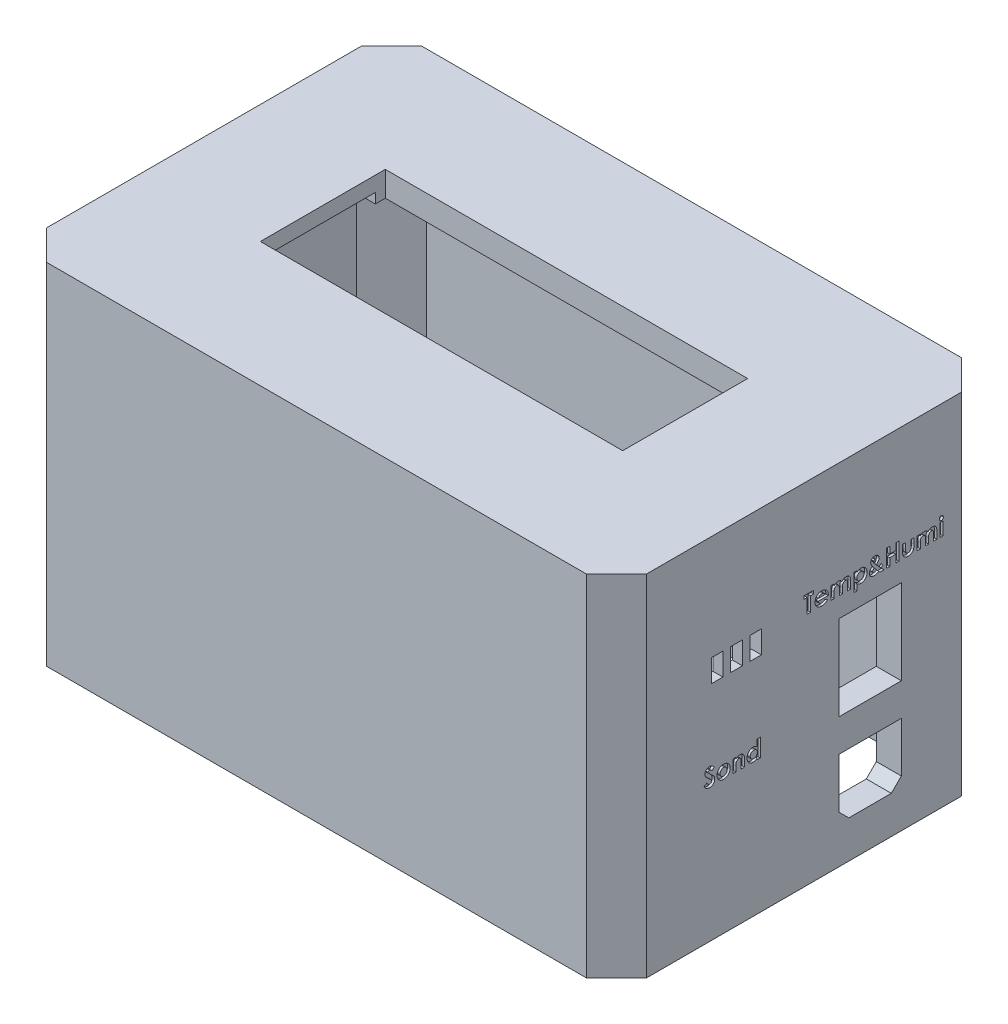
SolidWorks part; units mm, degrees
material "ABS"
ref_plane "Front Plane" through (0, 0, 0) normal (0, 0, 1) x (1, 0, 0)
ref_plane "Top Plane" through (0, 0, 0) normal (0, 1, 0) x (1, 0, 0)
ref_plane "Right Plane" through (0, 0, 0) normal (1, 0, 0) x (0, 0, -1)
sketch "Sketch1" plane through (0, 0, 0) normal (0, 1, 0) x (1, 0, 0)
  line L1 (-55, -32.5) -> (55, -32.5)
  line L2 (-55, -32.5) -> (-55, 32.5)
  line L3 (-55, 32.5) -> (55, 32.5)
  line L4 (55, -32.5) -> (55, 32.5)
  line L5 (-55, -32.5) -> (55, 32.5) construction
  line L6 (-55, 32.5) -> (55, -32.5) construction
  line L7 (-60, -37.5) -> (60, -37.5)
  line L8 (-60, -37.5) -> (-60, 37.5)
  line L9 (-60, 37.5) -> (60, 37.5)
  line L10 (60, -37.5) -> (60, 37.5)
  line L11 (-60, -37.5) -> (60, 37.5) construction
  line L12 (-60, 37.5) -> (60, -37.5) construction
  point P0 (0, 0)
  point P6 (0, 0)
  dimension "D1" = 110
  dimension "D2" = 65
  dimension "D3" = 5
  dimension "D4" = 5
extrude "Boss-Extrude1" add sketch "Sketch1" along normal blind 65
sketch "Sketch2" plane through (0, 65, 0) normal (0, 1, 0) x (1, 0, 0)
  line L1 (-60, 37.5) -> (60, 37.5)
  line L2 (-60, 37.5) -> (-60, -37.5)
  line L3 (-60, -37.5) -> (60, -37.5)
  line L4 (60, 37.5) -> (60, -37.5)
extrude "Boss-Extrude2" add sketch "Sketch2" along normal blind 5
chamfer "Chamfer1" distance 6 angle 45 4 edges at (60, 35, 37.5) (60, 35, -37.5) (-60, 35, -37.5) (-60, 35, 37.5)
chamfer "Chamfer2" distance 7 angle 45 4 edges at (-55, 32.5, -32.5) (55, 32.5, -32.5) (-55, 32.5, 32.5) (55, 32.5, 32.5)
sketch "Sketch3" plane through (0, 0, 0) normal (0, -1, 0) x (1, 0, 0)
  line L0 (-54, 37.5) -> (54, 37.5) construction
  line L1 (60, 31.5) -> (60, -31.5) construction
  line L2 (54, -37.5) -> (-54, -37.5) construction
  line L3 (-60, -31.5) -> (-60, 31.5) construction
  circle A0 centre (54.5, 32) radius 1.4
  circle A1 centre (-54.5, 32) radius 1.4
  circle A2 centre (-54.5, -32) radius 1.4
  circle A3 centre (54.5, -32) radius 1.4
  dimension "D1" = 2.8
  dimension "D2" = 5.5
  dimension "D3" = 5.5
  dimension "D4" = 2.8
  dimension "D6" = 5.5
  dimension "D7" = 2.8
  dimension "D8" = 5.5
  dimension "D9" = 5.5
  dimension "D10" = 2.8
  dimension "D11" = 5.5
  dimension "D12" = 5.5
  dimension "D5" = 5.5
extrude "Cut-Extrude1" cut sketch "Sketch3" against normal blind 35
chamfer "Chamfer3" distance 1.2 angle 45 4 edges at (-54.5, 35, -33.4) (54.5, 35, -33.4) (54.5, 35, 30.6) (-54.5, 35, 30.6)
sketch "Sketch4" plane through (0, 70, 0) normal (0, 1, 0) x (1, 0, 0)
  line L1 (36.25, -12.5) -> (-36.25, -12.5)
  line L2 (36.25, -12.5) -> (36.25, 12.5)
  line L3 (36.25, 12.5) -> (-36.25, 12.5)
  line L4 (-36.25, -12.5) -> (-36.25, 12.5)
  line L5 (36.25, -12.5) -> (-36.25, 12.5) construction
  line L6 (36.25, 12.5) -> (-36.25, -12.5) construction
  point P0 (0, 0)
  dimension "D1" = 72.5
  dimension "D2" = 25
extrude "Cut-Extrude2" cut sketch "Sketch4" against normal blind 5
sketch "Sketch5" plane through (0, 65, 0) normal (0, -1, 0) x (1, 0, 0)
  line L0 (-36.25, -12.5) -> (-36.25, 12.5) construction
  line L1 (-36.25, 10.5) -> (-44.25, 10.5)
  line L2 (-36.25, 10.5) -> (-36.25, -10.5)
  line L3 (-36.25, -10.5) -> (-44.25, -10.5)
  line L4 (-44.25, 10.5) -> (-44.25, -10.5)
  line L5 (-36.25, 12.5) -> (36.25, 12.5) construction
  line L6 (36.25, -12.5) -> (-36.25, -12.5) construction
  dimension "D1" = 2
  dimension "D2" = 2
  dimension "D3" = 8
extrude "Cut-Extrude3" cut sketch "Sketch5" against normal blind 2
chamfer "Chamfer4" distance 5 angle 45 2 edges at (-44.25, 66, -10.5) (-44.25, 66, 10.5)
sketch "Sketch6" plane through (60, 0, 0) normal (1, 0, 0) x (0, 0, -1)
  line L0 (31.5, 0) -> (31.5, 70) construction
  line L1 (7, 43) -> (19.5, 43)
  line L2 (7, 43) -> (7, 26)
  line L3 (7, 26) -> (19.5, 26)
  line L4 (19.5, 43) -> (19.5, 26)
  line L5 (7, 19.5) -> (19.5, 19.5)
  line L6 (7, 19.5) -> (7, 7.5)
  line L7 (7, 7.5) -> (19.5, 7.5)
  line L8 (19.5, 19.5) -> (19.5, 7.5)
  line L10 (-31.5, 70) -> (31.5, 70) construction
  dimension "D1" = 12.5
  dimension "D2" = 17
  dimension "D3" = 6.5
  dimension "D4" = 12.5
  dimension "D5" = 12
  dimension "D6" = 12
  dimension "D7" = 27
extrude "Cut-Extrude4" cut sketch "Sketch6" against normal blind 5
chamfer "Chamfer5" distance 2 angle 45 2 edges at (57.5, 7.5, -7) (57.5, 7.5, -19.5)
sketch "Sketch7" plane through (60, 0, 0) normal (1, 0, 0) x (0, 0, -1)
  text T0 "<b>Temp&Humi</b>"
extrude "Cut-Extrude6" cut sketch "Sketch7" against normal blind 0.5
sketch "Sketch8" plane through (60, 0, 0) normal (1, 0, 0) x (0, 0, -1)
  line L0 (19.5, 43) -> (7, 43) construction
  line L1 (-14.5, 43) -> (-12.5, 43)
  line L2 (-14.5, 43) -> (-14.5, 34)
  line L3 (-14.5, 34) -> (-12.5, 34)
  line L4 (-12.5, 43) -> (-12.5, 34)
  line L5 (-31.5, 70) -> (-31.5, 0) construction
  dimension "D1" = 0
  dimension "D2" = 9
  dimension "D3" = 2
  dimension "D4" = 17
extrude "Cut-Extrude7" cut sketch "Sketch8" against normal blind 5
sketch "Sketch9" plane through (0, 43, 0) normal (0, -1, 0) x (1, 0, 0)
  line L0 (55, 12.5) -> (55, 14.5) construction
  circle A0 centre (55, 13.5) radius 5
  dimension "D1" = 10
extrude "Cut-Extrude8" cut sketch "Sketch9" along normal blind 9
sketch "Sketch10" plane through (60, 0, 0) normal (1, 0, 0) x (0, 0, -1)
  line L0 (-14.5, 43) -> (-14.5, 34) construction
  line L1 (-16, 43) -> (-11, 43)
  line L2 (-16, 43) -> (-16, 34)
  line L3 (-16, 34) -> (-11, 34)
  line L4 (-11, 43) -> (-11, 34)
  line L5 (-12.5, 34) -> (-12.5, 43) construction
  dimension "D1" = 1.5
  dimension "D2" = 1.5
extrude "Cut-Extrude9" cut sketch "Sketch10" against normal blind 9
sketch "Sketch11" plane through (55, 0, 0) normal (-1, 0, 0) x (0, 0, 1)
  line L0 (8.5, 34) -> (8.5, 43) construction
  line L1 (6.5, 43) -> (20.5, 43)
  line L2 (6.5, 43) -> (6.5, 51)
  line L3 (6.5, 51) -> (20.5, 51)
  line L4 (20.5, 43) -> (20.5, 51)
  line L5 (18.5, 43) -> (18.5, 34) construction
  dimension "D1" = 2
  dimension "D2" = 2
  dimension "D3" = 8
extrude "Boss-Extrude4" add sketch "Sketch11" along normal blind 6
sketch "Sketch12" plane through (60, 0, 0) normal (1, 0, 0) x (0, 0, -1)
  line L1 (-18.5, 43) -> (-8.5, 43)
  line L2 (-18.5, 43) -> (-18.5, 49)
  line L3 (-18.5, 49) -> (-8.5, 49)
  line L4 (-8.5, 43) -> (-8.5, 49)
  line L5 (-11, 43) -> (-16, 43) construction
  line L6 (-11, 34) -> (-11, 43) construction
  dimension "D1" = 10
  dimension "D2" = 0
  dimension "D3" = 2.5
  dimension "D4" = 6
extrude "Cut-Extrude10" cut sketch "Sketch12" against normal blind 9
chamfer "Chamfer6" distance 6 angle 45 1 edges at (51, 49, 13.5)
chamfer "Chamfer7" distance 6 angle 45 1 edges at (49, 51, 13.5)
sketch "Sketch14" plane through (60, 0, 0) normal (1, 0, 0) x (0, 0, -1)
  line L0 (-8.5, 43) -> (-8.5, 49) construction
  line L1 (-18.5, 43) -> (-8.5, 43)
  line L2 (-18.5, 43) -> (-18.5, 44.5)
  line L3 (-18.5, 44.5) -> (-16.2, 44.5)
  line L4 (-8.5, 43) -> (-8.5, 44.5)
  line L5 (-8.5, 49) -> (-18.5, 49) construction
  line L6 (-16.2, 49) -> (-14.7, 49)
  line L7 (-16.2, 49) -> (-16.2, 44.5)
  line L8 (-10.8, 44.5) -> (-8.5, 44.5)
  line L9 (-14.7, 49) -> (-14.7, 44.5)
  line L10 (-18.5, 49) -> (-18.5, 43) construction
  line L11 (-12.3, 49) -> (-10.8, 49)
  line L12 (-12.3, 49) -> (-12.3, 44.5)
  line L14 (-10.8, 49) -> (-10.8, 44.5)
  line L15 (-14.7, 44.5) -> (-12.3, 44.5)
  point P19 (-18.5, 46)
  dimension "D1" = 1.5
  dimension "D2" = 1.5
  dimension "D3" = 1.5
  dimension "D4" = 2.3
  dimension "D5" = 2.3
extrude "Boss-Extrude6" add sketch "Sketch14" against normal blind 2
sketch "Sketch15" plane through (-60, 0, 0) normal (-1, 0, 0) x (0, 0, 1)
  line L0 (-31.5, 0) -> (31.5, 0) construction
  line L1 (-19.5, 0) -> (-4.5, 0)
  line L2 (-19.5, 0) -> (-19.5, 19)
  line L3 (-19.5, 19) -> (-4.5, 19)
  line L4 (-4.5, 0) -> (-4.5, 19)
  line L5 (31.5, 0) -> (31.5, 70) construction
  line L6 (14.5, 0) -> (24.5, 0)
  line L7 (14.5, 0) -> (14.5, 17)
  line L8 (14.5, 17) -> (24.5, 17)
  line L9 (24.5, 0) -> (24.5, 17)
  dimension "D1" = 10
  dimension "D2" = 15
  dimension "D3" = 2
  dimension "D4" = 19
  dimension "D5" = 19
  dimension "D6" = 7
extrude "Cut-Extrude11" cut sketch "Sketch15" against normal blind 5
fillet "Fillet1" radius 1.5 4 edges at (-57.5, 17, 24.5) (-57.5, 17, 14.5) (-57.5, 19, -19.5) (-57.5, 19, -4.5)
sketch "Sketch16" plane through (-60, 0, 0) normal (-1, 0, 0) x (0, 0, 1)
  line L0 (-6, 19) -> (-18, 19) construction
  line L1 (0, 30) -> (12, 30)
  line L2 (0, 30) -> (0, 42)
  line L3 (0, 42) -> (12, 42)
  line L4 (12, 30) -> (12, 42)
  line L5 (0, 45.5) -> (12, 45.5)
  line L6 (0, 45.5) -> (0, 57.5)
  line L7 (0, 57.5) -> (12, 57.5)
  line L8 (12, 45.5) -> (12, 57.5)
  dimension "D1" = 12
  dimension "D2" = 12
  dimension "D3" = 3.5
  dimension "D4" = 12
  dimension "D5" = 12
  dimension "D6" = 11
extrude "Cut-Extrude12" cut sketch "Sketch16" against normal blind 5
sketch "Sketch17" plane through (60, 0, 0) normal (1, 0, 0) x (0, 0, -1)
  text T0 "<b>Sond</b>"
extrude "Cut-Extrude13" cut sketch "Sketch17" against normal blind 0.5
chamfer "Chamfer8" distance 2 angle 45 2 edges at (-57.5, 30, 12) (-57.5, 30, 0)
sketch "Sketch18" plane through (0, 0, 11) normal (0, 0, 1) x (1, 0, 0)
  line L1 (60, 43) -> (59.3301, 43)
  line L2 (60, 43) -> (60, 34)
  line L3 (60, 34) -> (59.3301, 34)
  line L4 (59.3301, 43) -> (59.3301, 34)
extrude "Boss-Extrude7" add sketch "Sketch18" along normal blind 5
